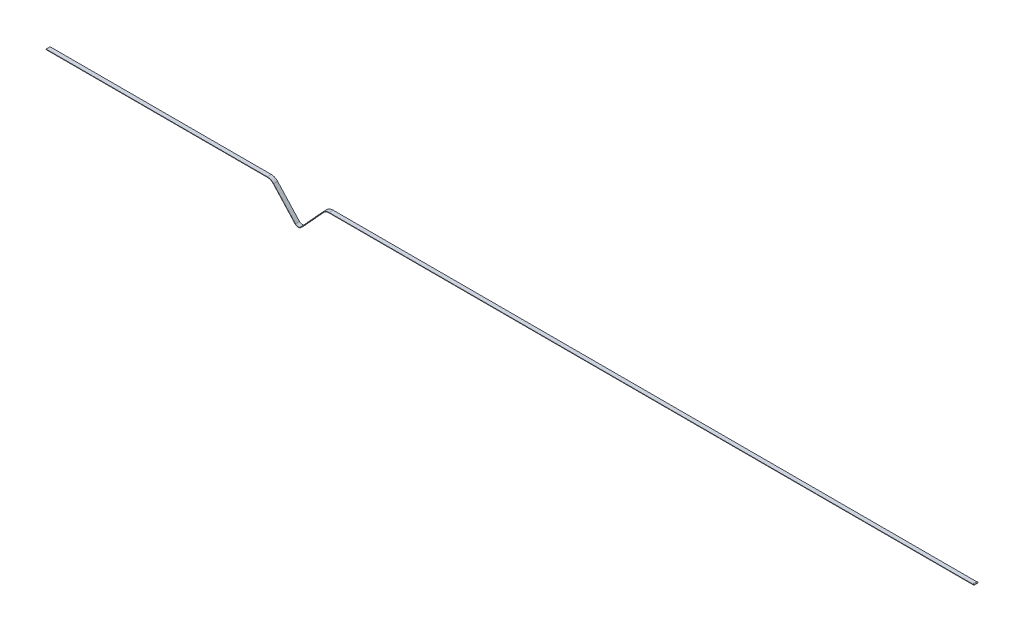
SolidWorks part; units mm, degrees
material "BUTYL"
ref_plane "Front Plane" through (0, 0, 0) normal (0, 0, 1) x (1, 0, 0)
ref_plane "Top Plane" through (0, 0, 0) normal (0, 1, 0) x (1, 0, 0)
ref_plane "Right Plane" through (0, 0, 0) normal (1, 0, 0) x (0, 0, -1)
sketch "Sketch1" plane through (0, 0, 0) normal (1, 0, 0) x (0, 0, -1)
  line L1 (0, 0) -> (6, 0)
  line L2 (0, 0) -> (0, 0.63)
  line L3 (0, 0.63) -> (6, 0.63)
  line L4 (6, 0) -> (6, 0.63)
  dimension "D1" = 0.63
  dimension "D2" = 6
sketch "Sketch2" plane through (0, 0, 0) normal (0, 0, 1) x (1, 0, 0)
  line L0 (0, 0) -> (-953.346, 0)
  line L1 (-962.165, -3.886) -> (-994.4069, -39.1468)
  line L2 (-1003.4251, -39.1468) -> (-1035.667, -3.886)
  line L3 (-1044.486, 0) -> (-1371.6, 0)
  arc A0 (-953.346, 0) -> (-962.165, -3.886) centre (-953.346, -11.95) ccw
  arc A1 (-994.4069, -39.1468) -> (-1003.4251, -39.1468) centre (-998.916, -35.0237) cw
  arc A2 (-1035.667, -3.886) -> (-1044.486, 0) centre (-1044.486, -11.95) ccw
  circle A3 centre (-953.346, -11.95) radius 11.95 construction
  circle A4 centre (-1044.486, -11.95) radius 11.95 construction
  circle A5 centre (-998.916, -35.0237) radius 6.11 construction
  dimension "D1" = 6.11
  dimension "D4" = 1371.6
sweep "Sweep1" add profiles "Sketch1" path "Sketch2"
sketch "Sketch3" plane through (0, 0, 0) normal (0, 0, 1) x (1, 0, 0)
  line L0 (0, 0.63) -> (-953.346, 0.63) construction
  line L1 (-1.5, 0.63) -> (-1.5, 0)
  line L2 (0, 0) -> (-953.346, 0) construction
  line L3 (-1.5, 0) -> (0, 0)
  line L4 (0, 0) -> (0, 0.63)
  arc A1 (0, 0.63) -> (-1.5, 0.63) centre (-0.75, 0.63) ccw
  dimension "D1" = 0.75
extrude "Boss-Extrude1" add sketch "Sketch3" against normal through all
pattern_curve "CrvPattern1" [suppressed] of bodies 102 driven by "Sketch2" parameters "D1"=2000, "D3"=2, "D2"=1, "D4"=10
